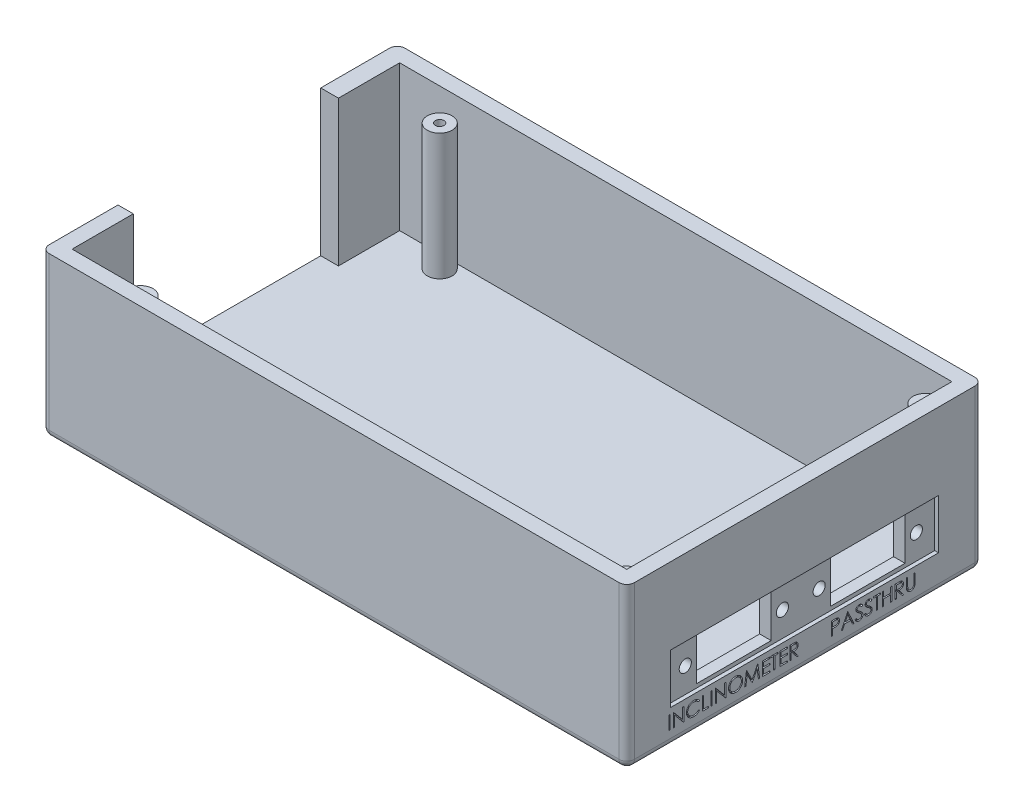
SolidWorks part; units mm, degrees
ref_plane "Front Plane" through (0, 0, 0) normal (0, 0, 1) x (1, 0, 0)
ref_plane "Top Plane" through (0, 0, 0) normal (0, 1, 0) x (1, 0, 0)
ref_plane "Right Plane" through (0, 0, 0) normal (1, 0, 0) x (0, 0, -1)
sketch "Sketch4" plane through (0, 0, 0) normal (0, 1, 0) x (1, 0, 0)
  line L1 (0, 0) -> (153, 0)
  line L2 (0, 0) -> (0, 93)
  line L3 (0, 93) -> (153, 93)
  line L4 (153, 0) -> (153, 93)
  line L5 (76.5, 93) -> (76.5, 0) construction
  line L6 (0, 46.5) -> (153, 46.5) construction
  point P484 (76.5, 46.5)
  dimension "D1" = 153
  dimension "D2" = 93
extrude "Boss-Extrude2" add sketch "Sketch4" against normal blind 4
sketch "Sketch5" plane through (0, 0, 0) normal (0, 1, 0) x (1, 0, 0)
  line L0 (0, 93) -> (153, 93)
  line L1 (153, 93) -> (153, 0)
  line L2 (153, 0) -> (0, 0)
  line L3 (0, 0) -> (0, 20)
  line L4 (0, 93) -> (0, 0) construction
  line L5 (0, 20) -> (4, 20)
  line L6 (4, 20) -> (4, 4)
  line L7 (4, 4) -> (149, 4)
  line L8 (149, 4) -> (149, 89)
  line L9 (149, 89) -> (4.627, 89)
  line L10 (4.627, 89) -> (4.627, 73)
  line L11 (4.627, 73) -> (0, 73)
  line L12 (0, 73) -> (0, 93)
  point P4 (4, 12)
  dimension "D1" = 20
  dimension "D2" = 85
  dimension "D3" = 145
  dimension "D4" = 20
  dimension "D5" = 4
  dimension "D6" = 4
  dimension "D7" = 4
extrude "Boss-Extrude4" add sketch "Sketch5" along normal blind 38
fillet "Fillet1" radius 2 8 edges at (153, -4, -46.5) (76.5, -4, -93) (76.5, -4, 0) (0, -4, -46.5) (153, 17, -93) (153, 17, 0) (0, 17, -93) (0, 17, 0)
sketch "Sketch6" plane through (0, 0, 0) normal (0, 1, 0) x (1, 0, 0)
  line L1 (145.5, 7.4) -> (18.5, 7.4)
  line L2 (145.5, 7.4) -> (145.5, 85.6)
  line L3 (145.5, 85.6) -> (18.5, 85.6)
  line L4 (18.5, 7.4) -> (18.5, 85.6)
  line L5 (82, 85.6) -> (82, 7.4) construction
  line L6 (145.5, 46.5) -> (18.5, 46.5) construction
  line L7 (149, 4) -> (4, 4) construction
  line L9 (4.627, 89) -> (149, 89) construction
  line L10 (149, 89) -> (149, 4) construction
  point P10 (0, 0)
  point P484 (82, 46.5)
  dimension "D1" = 127
  dimension "D2" = 78.2
  dimension "D3" = 42.5
  dimension "D4" = 42.5
  dimension "D5" = 3.5
sketch "Sketch7" plane through (0, 0, 0) normal (0, 1, 0) x (1, 0, 0)
  circle A0 centre (145.5, 7.4) radius 3.25
  circle A1 centre (18.5, 7.4) radius 3.25
  circle A2 centre (18.5, 85.6) radius 3.25
  circle A3 centre (145.5, 85.6) radius 3.25
  point P3 (145.5, 85.6)
  dimension "D1" = 2
  dimension "D3" = 6.5
  dimension "D2" = 2
extrude "Boss-Extrude5" add sketch "Sketch7" along normal blind 33
hole_wizard "#4-40 Tapped Hole1" positions "Sketch8" profile "Sketch9" tap size "#4-40" standard "ANSI Inch"
sketch "Sketch8" plane through (0, 33, 0) normal (0, 1, 0) x (1, 0, 0)
  point P0 (145.5, 7.4)
  point P3 (145.5, 85.6)
  point P6 (18.5, 7.4)
  point P9 (18.5, 85.6)
sketch "Sketch9" plane through (145.5, 33, -7.4) normal (1, 0, 0) x (0, 0, 1)
  line L0 (0, 0) -> (0, 20.6792)
  line L1 (0, 20.6792) -> (1.1303, 20)
  line L2 (1.1303, 20) -> (1.1303, 0)
  line L5 (1.1303, 0) -> (0, 0)
  line L10 (0, 20.6792) -> (-1.1303, 20) construction
  line L11 (0, -6.35) -> (0, 107.95) construction
  dimension "Tap Drill Dia." = 2.2606
  dimension "Tap Drill Depth" = 20
  dimension "Drill Angle" = 118
sketch "Sketch10" plane through (0, 0, 0) normal (0, 1, 0) x (1, 0, 0)
  line L1 (18.5, 85.6) -> (20.4, 85.6) construction
  line L2 (18.5, 85.6) -> (7, 85.6) construction
  line L3 (18.5, 85.6) -> (18.5, 9.4) construction
  line L4 (18.5, 9.4) -> (7, 9.4) construction
  line L5 (7, 85.6) -> (7, 9.4) construction
  dimension "D1" = 11.5
  dimension "D2" = 76.2
sketch "Sketch11" plane through (153, 0, 0) normal (1, 0, 0) x (0, 0, -1)
  line L0 (2, 38) -> (2, -2) construction
  line L1 (73.75, 17) -> (54.25, 17)
  line L2 (73.75, 17) -> (73.75, 6)
  line L3 (73.75, 6) -> (54.25, 6)
  line L4 (54.25, 17) -> (54.25, 6)
  line L5 (38.75, 17) -> (19.25, 17)
  line L6 (38.75, 17) -> (38.75, 6)
  line L7 (38.75, 6) -> (19.25, 6)
  line L8 (19.25, 17) -> (19.25, 6)
  line L9 (29, 6) -> (29, 17) construction
  line L10 (38.75, 11.5) -> (19.25, 11.5) construction
  line L15 (64, 17) -> (64, 6) construction
  line L16 (65.5654, 11.5) -> (73.75, 11.5) construction
  line L17 (91, -2) -> (91, 38) construction
  line L18 (2, -2) -> (91, -2) construction
  line L19 (73.75, 11.5) -> (54.25, 11.5) construction
  circle A0 centre (76.7, 11.5) radius 1.5875
  circle A1 centre (51.3, 11.5) radius 1.5875
  circle A2 centre (41.7, 11.5) radius 1.5875
  circle A3 centre (16.3, 11.5) radius 1.5875
  point P8 (76.7, 11.5)
  point P11 (51.3, 11.5)
  point P12 (41.7, 11.5)
  point P13 (16.3, 11.5)
  point P34 (64, 11.5)
  point P232 (29, 11.5)
  point P246 (64, 17)
  dimension "D12" = 8
  dimension "D13" = 3.175
  dimension "D1" = 19.5
  dimension "D2" = 19.5
  dimension "D3" = 11
  dimension "D4" = 11
  dimension "D5" = 12.7
  dimension "D6" = 12.7
  dimension "D7" = 12.7
  dimension "D8" = 12.7
  dimension "D9" = 15.5
  dimension "D10" = 17.25
  dimension "D11" = 17.25
extrude "Cut-Extrude1" cut sketch "Sketch11" against normal up to surface (4 mm away) up to face at (149, 19, -46.5)
sketch "Sketch12" plane through (153, 0, 0) normal (1, 0, 0) x (0, 0, -1)
  line L0 (19.25, 6) -> (38.75, 6) construction
  line L1 (11.5, 18) -> (81.5, 18)
  line L2 (11.5, 18) -> (11.5, 5)
  line L3 (11.5, 5) -> (81.5, 5)
  line L4 (81.5, 18) -> (81.5, 5)
  line L5 (38.75, 17) -> (19.25, 17) construction
  circle A0 centre (16.3, 11.5) radius 1.5875 construction
  circle A1 centre (76.7, 11.5) radius 1.5875 construction
  dimension "D1" = 13
  dimension "D2" = 1
  dimension "D3" = 1
  dimension "D4" = 70
  dimension "D5" = 4.8
  dimension "D6" = 4.8
extrude "Cut-Extrude2" cut sketch "Sketch12" against normal blind 1
sketch "Sketch13" plane through (153, 0, 0) normal (1, 0, 0) x (0, 0, -1)
  text T0 "INCLINOMETER"
  text T1 "PASSTHRU"
extrude "Cut-Extrude3" cut sketch "Sketch13" against normal blind 0.5
sketch "Sketch14" plane through (0, 0, 0) normal (-1, 0, 0) x (0, 0, 1)
  text T0 "12VDC\r\ncenter +" font "Century Gothic" height 3.5
extrude "Cut-Extrude4" cut sketch "Sketch14" against normal blind 0.5
